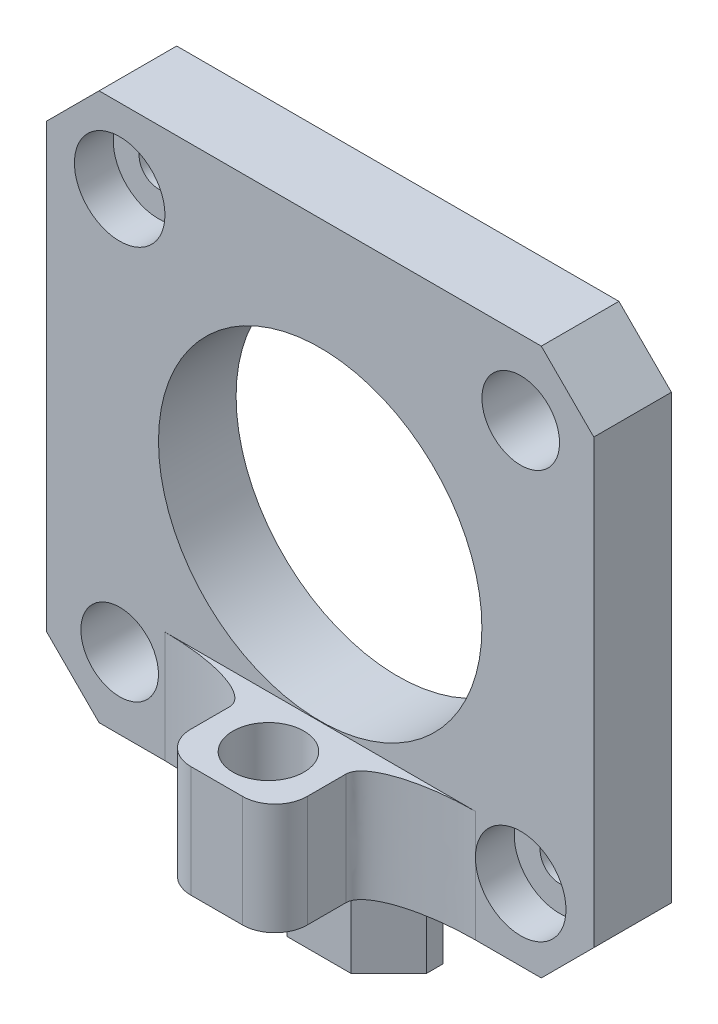
SolidWorks part; units mm, degrees
ref_plane "Front Plane" through (0, 0, 0) normal (0, 0, 1) x (1, 0, 0)
ref_plane "Top Plane" through (0, 0, 0) normal (0, 1, 0) x (1, 0, 0)
ref_plane "Right Plane" through (0, 0, 0) normal (1, 0, 0) x (0, 0, -1)
sketch "Sketch1" plane through (0, 0, 0) normal (0, 0, 1) x (1, 0, 0)
  line L0 (-21150, 17212.9994) -> (-17091.7811, 21271.2183)
  line L1 (-17091.7811, -21028.7817) -> (17091.7811, -21028.7817)
  line L2 (-21150, -16970.5627) -> (-21150, 17212.9994)
  line L3 (-17091.7811, 21271.2183) -> (17091.7811, 21271.2183)
  line L4 (21150, -16970.5627) -> (21150, 17212.9994)
  line L5 (-29910.6168, -90.9137) -> (30333.0875, 92.1978) construction
  line L6 (0, 29819.7031) -> (0, -29577.2665) construction
  line L7 (17091.7811, 21271.2183) -> (21150, 17212.9994)
  line L8 (17091.7811, -21028.7817) -> (21150, -16970.5627)
  line L9 (-17091.7811, -21028.7817) -> (-21150, -16970.5627)
  arc A0 (-17091.7811, -21028.7817) -> (17091.7811, -21028.7817) centre (0, 121.2183) ccw construction
  arc A1 (21150, -16970.5627) -> (21150, 17212.9994) centre (0, 121.2183) ccw construction
  arc A2 (17091.7811, 21271.2183) -> (-17091.7811, 21271.2183) centre (0, 121.2183) ccw construction
  arc A3 (-21150, 17212.9994) -> (-21150, -16970.5627) centre (0, 121.2183) ccw construction
  circle A4 centre (0, 121.2183) radius 11025
  point P0 (0, 0)
  dimension "D2" = 42300
  dimension "D3" = 22050
  dimension "D1" = 42300
extrude "Boss-Extrude1" add sketch "Sketch1" along normal blind 5000
sketch "Sketch2" plane through (0, 0, 5000) normal (0, 0, 1) x (1, 0, 0)
  line L0 (0, -21028.7817) -> (0, -11028.7817) construction
  line L1 (-17091.7811, -21028.7817) -> (17091.7811, -21028.7817) construction
  line L2 (0, -11028.7817) -> (4500, -11028.7817)
  line L3 (4500, -11028.7817) -> (4500, -21028.7817)
  line L4 (4500, -21028.7817) -> (-4500, -21028.7817)
  line L5 (-4500, -21028.7817) -> (-4500, -11028.7817)
  line L6 (-4500, -11028.7817) -> (0, -11028.7817)
  dimension "D1" = 9000
extrude "Boss-Extrude2" add sketch "Sketch2" along normal blind 8000
sketch "Sketch4" plane through (0, 0, 5000) normal (0, 0, 1) x (1, 0, 0)
  line L1 (-15500, -15500) -> (15500, -15500) construction
  line L2 (-15500, -15500) -> (-15500, 15500) construction
  line L3 (-15500, 15500) -> (15500, 15500) construction
  line L4 (15500, -15500) -> (15500, 15500) construction
  line L5 (-15500, -15500) -> (15500, 15500) construction
  line L6 (-15500, 15500) -> (15500, -15500) construction
  circle A0 centre (-15500, 15500) radius 3000
  circle A1 centre (15500, 15500) radius 3000
  circle A2 centre (15500, -15500) radius 3000
  circle A3 centre (-15500, -15500) radius 3000
  point P0 (0, 0)
  dimension "D1" = 6000
  dimension "D2" = 31000
  dimension "D3" = 31000
extrude "Cut-Extrude2" cut sketch "Sketch4" against normal blind 3000
sketch "Sketch5" plane through (0, 0, 2000) normal (0, 0, 1) x (1, 0, 0)
  circle A0 centre (-15500, 15500) radius 1500
  circle A1 centre (15500, -15500) radius 1500
extrude "Cut-Extrude3" cut sketch "Sketch5" against normal blind 3000
sketch "Sketch6" plane through (0, 0, 2000) normal (0, 0, 1) x (1, 0, 0)
  circle A1 centre (15500, 15500) radius 3000
  circle A2 centre (15500, 15500) radius 3000
  circle A3 centre (-15500, -15500) radius 3000
  circle A4 centre (-15500, -15500) radius 3000
  dimension "D1" = 0
  dimension "D2" = 0
extrude "Cut-Extrude4" cut sketch "Sketch6" against normal blind 3000
sketch "Sketch3" plane through (0, -21028.7817, 0) normal (0, -1, 0) x (1, 0, 0)
  line L0 (-4500, 5000) -> (4500, 13000) construction
  line L1 (-4500, 13000) -> (4500, 5000) construction
  circle A0 centre (0, 9000) radius 2900
extrude "Cut-Extrude1" cut sketch "Sketch3" against normal blind 12018
scale "Scale6" scale about centroid uniform scaling yes scale factor 0.001
sketch "Croquis1" plane through (0, 0, 2916.1616) normal (0, 0, 1) x (1, 0, 0)
  circle A0 centre (0, -944.1916) radius 12.5
  dimension "D1" = 25
extrude "Cortar-Extruir1" cut sketch "Croquis1" against normal blind 10 and the other way blind 10
sketch "Croquis2" plane through (0, 0, 2924.1616) normal (0, 0, 1) x (1, 0, 0)
  line L0 (4.5, -965.3416) -> (4.5, -955.8536) construction
  line L1 (-4.5, -955.8536) -> (4.5, -955.8536)
  line L2 (-4.5, -955.8536) -> (-4.5, -956.73)
  line L3 (-4.5, -956.73) -> (4.5, -956.73)
  line L4 (4.5, -955.8536) -> (4.5, -956.73)
extrude "Cortar-Extruir2" cut sketch "Croquis2" against normal up to surface (8 mm away) up to face at (18.5, -928.8129, 2916.1616)
sketch "Croquis4" plane through (0, -965.3416, 0) normal (0, -1, 0) x (1, 0, 0)
  circle A0 centre (0, 2920.1616) radius 2.9
  circle A1 centre (0, 2920.1616) radius 2.4
  dimension "D1" = 4.8
extrude "Saliente-Extruir2" add sketch "Croquis4" against normal up to surface (8.6116 mm away) up to face at (0, -956.73, 2920.1616)
sketch "Croquis5" plane through (0, 0, 2916.1616) normal (0, 0, 1) x (1, 0, 0)
  circle A0 centre (-15.5, -928.8129) radius 3.5
  circle A1 centre (15.5, -959.8129) radius 3.5
  dimension "D1" = 7
  dimension "D2" = 7
extrude "Cortar-Extruir3" cut sketch "Croquis5" against normal up to surface (3 mm away) up to face at (-14, -928.8129, 2913.1616)
sketch "Croquis6" plane through (0, 0, 2911.1616) normal (0, 0, -1) x (-1, 0, 0)
  line L12 (17.0918, -923.0416) -> (-17.0918, -923.0416)
  line L13 (-17.0918, -923.0416) -> (-21.15, -927.0999)
  line L14 (-21.15, -927.0999) -> (-21.15, -961.2834)
  line L15 (-21.15, -961.2834) -> (-17.0918, -965.3416)
  line L16 (-17.0918, -965.3416) -> (17.0918, -965.3416)
  line L21 (17.0918, -965.3416) -> (21.15, -961.2834)
  line L22 (21.15, -961.2834) -> (21.15, -927.0999)
  line L23 (21.15, -927.0999) -> (17.0918, -923.0416)
  line L24 (17.0918, -923.0416) -> (-17.0918, -923.0416)
  line L25 (-17.0918, -923.0416) -> (-21.15, -927.0999)
  line L26 (-21.15, -927.0999) -> (-21.15, -961.2834)
  line L27 (-21.15, -961.2834) -> (-17.0918, -965.3416)
  line L28 (-17.0918, -965.3416) -> (17.0918, -965.3416)
  line L33 (17.0918, -965.3416) -> (21.15, -961.2834)
  line L34 (21.15, -961.2834) -> (21.15, -927.0999)
  line L35 (21.15, -927.0999) -> (17.0918, -923.0416)
  circle A0 centre (15.5, -928.8129) radius 1.5918
  circle A1 centre (-15.5, -928.8129) radius 3
  circle A2 centre (-15.5, -959.8129) radius 1.5
  circle A3 centre (15.5, -959.8129) radius 3
  circle A4 centre (0, -944.1916) radius 12.5
  dimension "D1" = 0
extrude "Saliente-Extruir3" add sketch "Croquis6" along normal blind 1
fillet "Redondeo1" radius 2.5 2 edges at (4.5, -961.0358, 2924.1616) (-4.5, -961.0358, 2924.1616)
hole_wizard "Taladro de margen para M51" positions "Croquis3D1" profile "Croquis7" hole size "M5" standard "Ansi Metric"
sketch3d "Croquis3D1"
  line L0 (0, -956.73, 2920.1616) -> (0, -965.3416, 2920.1616) construction
  point P0 (0, -956.73, 2920.1616)
sketch "Croquis7" plane through (0, -956.73, 2920.1616) normal (1, 0, 0) x (0, 0, 1)
  line L0 (0, 0) -> (0, 10.263)
  line L1 (0, 10.263) -> (2.75, 8.6106)
  line L2 (2.75, 8.6106) -> (2.75, 0)
  line L5 (2.75, 0) -> (0, 0)
  line L10 (0, 10.263) -> (-2.75, 8.6106) construction
  line L11 (0, -6.35) -> (0, 107.95) construction
  dimension "Diámetro de taladro" = 5.5
  dimension "Profundidad de taladro" = 8.6106
  dimension "Ángulo de perforador" = 118
sketch "Croquis8" plane through (0, -965.3416, 0) normal (0, -1, 0) x (1, 0, 0)
  line L3 (-2.8793, 2912.0116) -> (-5.45, 2912.0116)
  line L4 (-5.45, 2912.0116) -> (-5.45, 2913.2909)
  line L5 (-5.45, 2913.2909) -> (-2.5293, 2916.2116)
  line L6 (-2.5293, 2916.2116) -> (2.4293, 2916.2116)
  line L7 (2.4293, 2916.2116) -> (5.35, 2913.2909)
  line L8 (5.35, 2913.2909) -> (5.35, 2912.0116)
  line L9 (5.35, 2912.0116) -> (2.8793, 2912.0116)
  line L13 (-2.8793, 2910.1616) -> (2.8793, 2910.1616)
  line L15 (-2.8793, 2912.0116) -> (-2.8793, 2910.1616)
  line L16 (2.8793, 2912.0116) -> (2.8793, 2910.1616)
  line L44 (-6.85, 2914.7616) -> (-8.2, 2914.7616)
  line L45 (-8.2, 2914.7616) -> (-8.2, 2917.1616)
  line L46 (-8.2, 2917.1616) -> (-10, 2915.3616)
  line L47 (-10, 2915.3616) -> (-10, 2910.1616)
  line L48 (-10, 2910.1616) -> (-4.8, 2910.1616)
  line L49 (-4.8, 2910.1616) -> (-3, 2911.9616)
  line L50 (-3, 2911.9616) -> (-5.5, 2911.9616)
  line L51 (-5.5, 2911.9616) -> (-5.5, 2913.3116)
  line L52 (-5.5, 2913.3116) -> (-2.55, 2916.2616)
  line L53 (-2.55, 2916.2616) -> (2.45, 2916.2616)
  line L54 (2.45, 2916.2616) -> (5.4, 2913.3116)
  line L55 (5.4, 2913.3116) -> (5.4, 2911.9616)
  line L56 (5.4, 2911.9616) -> (3, 2911.9616)
  line L57 (3, 2911.9616) -> (4.8, 2910.1616)
  line L58 (4.8, 2910.1616) -> (10, 2910.1616)
  line L59 (10, 2910.1616) -> (10, 2915.3616)
  line L60 (10, 2915.3616) -> (8.2, 2917.1616)
  line L61 (8.2, 2917.1616) -> (8.2, 2914.6616)
  line L62 (8.2, 2914.6616) -> (6.85, 2914.6616)
  line L63 (6.85, 2914.6616) -> (3.9, 2917.6116)
  line L64 (3.9, 2917.6116) -> (3.9, 2922.6116)
  line L65 (3.9, 2922.6116) -> (6.85, 2925.5616)
  line L66 (6.85, 2925.5616) -> (8.2, 2925.5616)
  line L67 (8.2, 2925.5616) -> (8.2, 2923.1616)
  line L68 (8.2, 2923.1616) -> (10, 2924.9616)
  line L69 (10, 2924.9616) -> (10, 2930.1616)
  line L70 (10, 2930.1616) -> (4.8, 2930.1616)
  line L71 (4.8, 2930.1616) -> (3, 2928.3616)
  line L72 (3, 2928.3616) -> (5.5, 2928.3616)
  line L73 (5.5, 2928.3616) -> (5.5, 2927.0116)
  line L74 (5.5, 2927.0116) -> (2.55, 2924.0616)
  line L75 (2.55, 2924.0616) -> (-2.45, 2924.0616)
  line L76 (-2.45, 2924.0616) -> (-5.4, 2927.0116)
  line L77 (-5.4, 2927.0116) -> (-5.4, 2928.3616)
  line L78 (-5.4, 2928.3616) -> (-3, 2928.3616)
  line L79 (-3, 2928.3616) -> (-4.8, 2930.1616)
  line L80 (-4.8, 2930.1616) -> (-10, 2930.1616)
  line L81 (-10, 2930.1616) -> (-10, 2924.9616)
  line L82 (-10, 2924.9616) -> (-8.2, 2923.1616)
  line L83 (-8.2, 2923.1616) -> (-8.2, 2925.6616)
  line L84 (-8.2, 2925.6616) -> (-6.85, 2925.6616)
  line L85 (-6.85, 2925.6616) -> (-3.9, 2922.7116)
  line L86 (-3.9, 2922.7116) -> (-3.9, 2917.7116)
  line L87 (-3.9, 2917.7116) -> (-6.85, 2914.7616)
  line L128 (-8.2, 2925.6616) -> (-6.85, 2925.6616)
  dimension "D1" = 0
extrude "Saliente-Extruir4" add sketch "Croquis8" along normal blind 7 contours L13 L16 L9 L8 L7 L6 L5 L4 L3 L15
fillet "Redondeo2" radius 7.5 2 edges at (4.5, -961.0358, 2916.1616) (-4.5, -961.0358, 2916.1616) second distance 2.5 first distance on face at (-12, -928.8129, 2916.1616)
